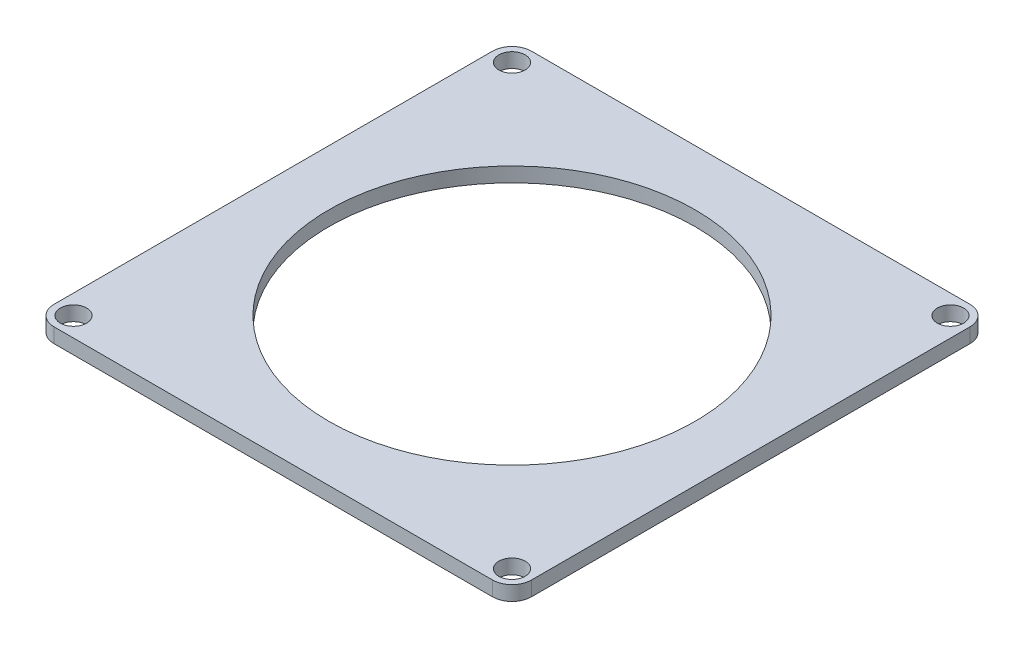
SolidWorks part; units mm, degrees
ref_plane "Front Plane" through (0, 0, 0) normal (0, 0, 1) x (1, 0, 0)
ref_plane "Top Plane" through (0, 0, 0) normal (0, 1, 0) x (1, 0, 0)
ref_plane "Right Plane" through (0, 0, 0) normal (1, 0, 0) x (0, 0, -1)
sketch "Эскиз1" plane through (0, 0, 0) normal (0, 1, 0) x (1, 0, 0)
  line L1 (-45, -49) -> (45, -49)
  line L2 (-49, -45) -> (-49, 45)
  line L3 (-45, 49) -> (45, 49)
  line L4 (49, -45) -> (49, 45)
  line L5 (-47.8284, -47.8284) -> (47.8284, 47.8284) construction
  line L6 (-47.8284, 47.8284) -> (47.8284, -47.8284) construction
  circle A0 centre (-45, 45) radius 4
  circle A2 centre (45, 45) radius 4
  circle A4 centre (-45, -45) radius 4
  circle A6 centre (45, -45) radius 4
  circle A8 centre (45, -45) radius 2.7
  point P0 (0, 0)
  dimension "D2" = 8
  dimension "D3" = 98
  dimension "D4" = 8
  dimension "D6" = 49
  dimension "D7" = 8
  dimension "D9" = 8
  dimension "D10" = 5.4
  dimension "D11" = 49
  dimension "D12" = 49
extrude "Бобышка-Вытянуть1" add sketch "Эскиз1" along normal blind 3 contours A8 A6 L4 A2 L3 A0 L2 A4 L1 | A0 | A2 | A6 A8 | A8 A6 | A4 | A6 A8 region at (0, 0, 0) region at (-45, 0, 45) region at (42.2516, 0, 42.2516) region at (-45, 0, -45) region at (45, 0, -45) region at (45, 0, 45)
sketch "Эскиз2" plane through (0, 3, 0) normal (0, 1, 0) x (1, 0, 0)
  circle A0 centre (0, 0) radius 37.6
  dimension "D1" = 75.2
extrude "Вырез-Вытянуть1" cut sketch "Эскиз2" against normal blind 3
sketch "Эскиз3" plane through (0, 0, 0) normal (1, 0, 0) x (0, 0, -1)
  line L0 (0, 0) -> (0, 2.3739) construction
extrude "Вырез-Вытянуть5" cut sketch "Эскиз1<4>" along normal blind 10 contours A8
sketch "Эскиз1<4>" plane through (0, 0, 0) normal (0, 1, 0) x (1, 0, 0) same geometry as "Эскиз1"
pattern_circular "Круговой массив2" count 4 over 360 about axis through (0, 0, 0) along (0, 1, 0) of "Вырез-Вытянуть5" reverse direction yes
